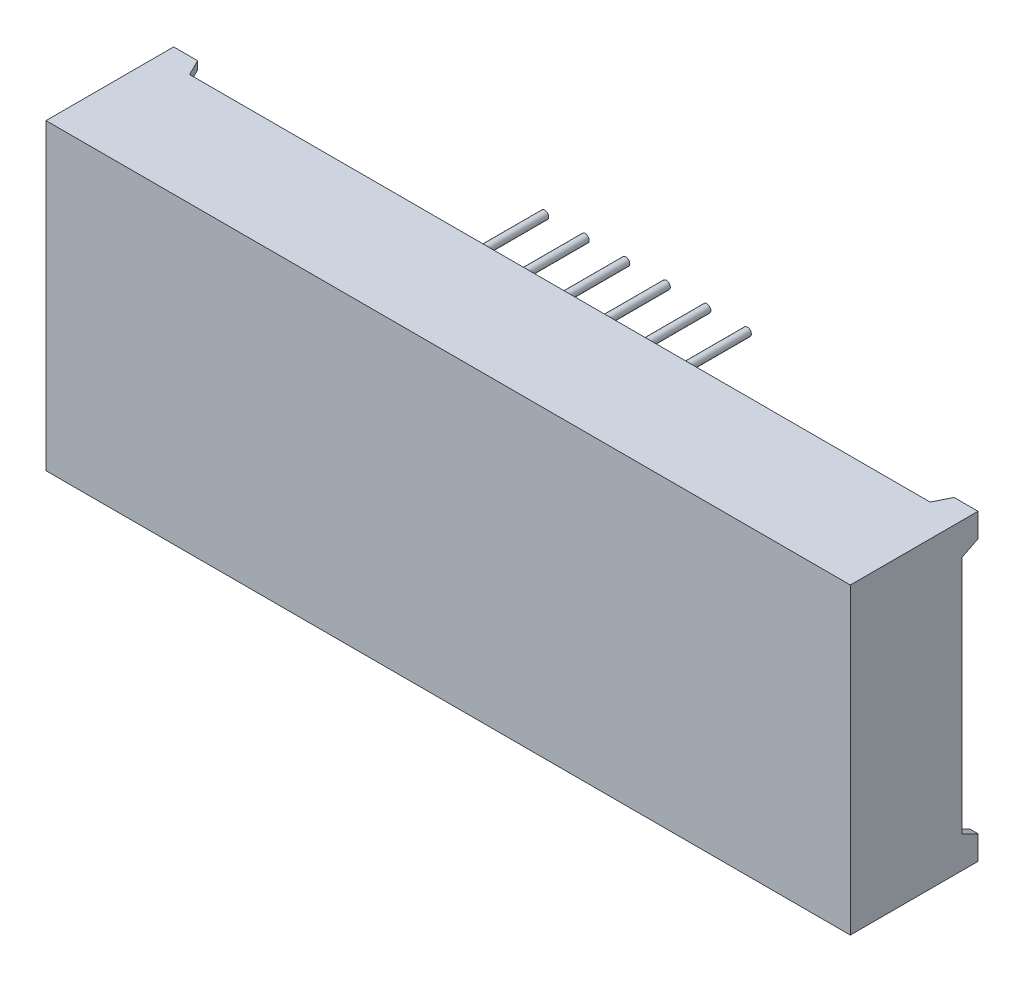
SolidWorks part; units mm, degrees
ref_plane "Front Plane" through (0, 0, 0) normal (0, 0, 1) x (1, 0, 0)
ref_plane "Top Plane" through (0, 0, 0) normal (0, 1, 0) x (1, 0, 0)
ref_plane "Right Plane" through (0, 0, 0) normal (1, 0, 0) x (0, 0, -1)
sketch "Sketch1" plane through (0, 0, 0) normal (0, 1, 0) x (1, 0, 0)
  line L1 (0, 0) -> (50.4, 0)
  line L2 (0, 0) -> (0, 8)
  line L3 (0, 8) -> (50.4, 8)
  line L4 (50.4, 0) -> (50.4, 8)
  dimension "D1" = 8
  dimension "D2" = 50.4
extrude "Boss-Extrude1" add sketch "Sketch1" along normal blind 19
sketch "Sketch2" plane through (0, 0, -8) normal (0, 0, -1) x (-1, 0, 0)
  line L0 (-50.4, 17) -> (-49.9, 17)
  line L1 (-50.4, 19) -> (-50.4, 0) construction
  line L2 (-49.9, 17) -> (-49.9, 18.5)
  line L3 (-49.9, 18.5) -> (-48.4, 18.5)
  line L4 (-48.4, 18.5) -> (-48.4, 19)
  line L5 (-50.4, 19) -> (0, 19) construction
  line L6 (-48.4, 19) -> (-2, 19)
  line L7 (-2, 19) -> (-2, 18.5)
  line L8 (-2, 18.5) -> (-0.5, 18.5)
  line L9 (-0.5, 18.5) -> (-0.5, 17)
  line L10 (-0.5, 17) -> (0, 17)
  line L11 (0, 19) -> (0, 0) construction
  line L12 (0, 17) -> (0, 2)
  line L13 (0, 2) -> (-0.5, 2)
  line L14 (-0.5, 2) -> (-0.5, 0.5)
  line L15 (-0.5, 0.5) -> (-2, 0.5)
  line L16 (-2, 0.5) -> (-2, 0)
  line L17 (-50.4, 0) -> (0, 0) construction
  line L18 (-2, 0) -> (-48.4, 0)
  line L19 (-48.4, 0) -> (-48.4, 0.5)
  line L20 (-48.4, 0.5) -> (-49.9, 0.5)
  line L21 (-49.9, 0.5) -> (-49.9, 2)
  line L22 (-49.9, 2) -> (-50.4, 2)
  line L23 (-50.4, 2) -> (-50.4, 17)
  line L24 (-49.9, 17) -> (-49.9, 2) construction
  line L25 (-48.4, 0.5) -> (-2, 0.5) construction
  line L26 (-0.5, 2) -> (-0.5, 17) construction
  line L27 (-2, 18.5) -> (-48.4, 18.5) construction
  line L28 (-2, 0.5) -> (-2, 18.5) construction
  line L29 (-0.5, 17) -> (-49.9, 17) construction
  line L30 (-48.4, 0.5) -> (-48.4, 18.5) construction
  line L31 (-49.9, 2) -> (-0.5, 2) construction
  dimension "D1" = 0.5
  dimension "D2" = 2
  dimension "D3" = 2
  dimension "D4" = 2
  dimension "D5" = 2
extrude "Cut-Extrude1" cut sketch "Sketch2" against normal blind 1
chamfer "Chamfer1" distance 0.5 distance2 1 8 edges at (50.15, 2, -8) (48.4, 0.25, -8) (2, 0.25, -8) (0.25, 2, -8) (2, 18.75, -8) (0.25, 17, -8) (48.4, 18.75, -8) (50.15, 17, -8) first distance on face at (49.5667, 0.8333, -8) first distance on face at (0.8333, 0.8333, -8) first distance on face at (0.8333, 18.1667, -8) first distance on face at (49.5667, 18.1667, -8)
sketch "Sketch3" plane through (0, 0, -7) normal (0, 0, -1) x (-1, 0, 0)
  line L21 (-49.9, 0.5) -> (-0.5, 0.5)
  line L22 (-49.9, 0.5) -> (-49.9, 18.5)
  line L23 (-49.9, 18.5) -> (-0.5, 18.5)
  line L24 (-0.5, 0.5) -> (-0.5, 18.5)
extrude "Cut-Extrude2" cut sketch "Sketch3" against normal blind 0.1
sketch "Sketch4" plane through (0, 0, -6.9) normal (0, 0, -1) x (-1, 0, 0)
  line L0 (-49.9, 9.5) -> (-0.5, 9.5) construction
  line L1 (-49.9, 2) -> (-49.9, 17) construction
  line L2 (-0.5, 0.5) -> (-0.5, 18.5) construction
  line L3 (-49.9, 17.12) -> (-0.5, 17.12) construction
  line L4 (-49.9, 18.5) -> (-49.9, 0.5) construction
  line L5 (-0.5, 1.88) -> (-49.9, 1.88) construction
  line L6 (-25.2, 1.88) -> (-25.2, 17.12) construction
  line L7 (-26.47, 17.12) -> (-25.2, 15.85) construction
  line L8 (-25.2, 15.85) -> (-23.93, 17.12) construction
  line L9 (-31.55, 17.12) -> (-31.55, 1.88) construction
  line L10 (-29.01, 17.12) -> (-29.01, 1.88) construction
  line L11 (-26.47, 17.12) -> (-26.47, 1.88) construction
  line L12 (-23.93, 17.12) -> (-23.93, 1.88) construction
  line L13 (-21.39, 17.12) -> (-21.39, 1.88) construction
  line L14 (-18.85, 17.12) -> (-18.85, 1.88) construction
  circle A0 centre (-31.55, 17.12) radius 0.25
  circle A1 centre (-29.01, 17.12) radius 0.25
  circle A2 centre (-26.47, 17.12) radius 0.25
  circle A3 centre (-23.93, 17.12) radius 0.25
  circle A4 centre (-21.39, 17.12) radius 0.25
  circle A5 centre (-18.85, 17.12) radius 0.25
  circle A6 centre (-31.55, 1.88) radius 0.25
  circle A7 centre (-29.01, 1.88) radius 0.25
  circle A8 centre (-26.47, 1.88) radius 0.25
  circle A10 centre (-23.93, 1.88) radius 0.25
  circle A11 centre (-21.39, 1.88) radius 0.25
  circle A12 centre (-18.85, 1.88) radius 0.25
  point P30 (-25.2, 9.5)
  dimension "D6" = 0.5
  dimension "D1" = 15.24
  dimension "D2" = 2.54
  dimension "D3" = 2.54
  dimension "D4" = 2.54
  dimension "D5" = 2.54
  dimension "D7" = 2.54
  dimension "D8" = 45
  dimension "D9" = 45
extrude "Boss-Extrude2" add sketch "Sketch4" along normal blind 5.5
sketch "Sketch5" plane through (0, 0, 0) normal (0, 0, 1) x (1, 0, 0)
  line L0 (0, 9.5) -> (50.4, 9.5) construction
  line L1 (0, 19) -> (0, 0) construction
  line L2 (50.4, 19) -> (50.4, 0) construction
  line L3 (49.0088, 15.4806) -> (48.1824, 9.6)
  line L4 (0, 19) -> (50.4, 19) construction
  line L5 (0, 0) -> (50.4, 0) construction
  line L6 (6.15, 19) -> (6.15, 0) construction
  line L7 (18.85, 0) -> (18.85, 19) construction
  line L8 (31.55, 0) -> (31.55, 19) construction
  line L9 (44.25, 0) -> (44.25, 19) construction
  line L10 (25.2, 9.5) -> (25.2, 19) construction
  line L11 (25.2, 14.25) -> (18.85, 14.25) construction
  line L12 (25.2, 14.25) -> (31.55, 14.25) construction
  line L13 (50.4, 16.61) -> (0, 16.61) construction
  line L14 (50.4, 2.39) -> (0, 2.39) construction
  line L15 (49.4, 16.61) -> (49.4, 9.5) construction
  line L16 (49.4, 9.5) -> (49.4, 2.39) construction
  line L17 (48.1824, 9.6) -> (47.6288, 9.6)
  line L18 (47.6288, 9.6) -> (47.2288, 10)
  line L19 (47.2288, 10) -> (48.1577, 16.61)
  line L20 (48.1824, 9.6) -> (48.1543, 9.4) construction
  line L21 (48.1543, 9.4) -> (47.2887, 3.2411)
  line L22 (48.1543, 9.4) -> (47.6288, 9.4)
  line L23 (47.6288, 9.4) -> (47.0652, 8.8365)
  line L24 (47.0652, 8.8365) -> (46.1592, 2.39)
  line L25 (47.4459, 9.5) -> (46.9459, 9)
  line L26 (46.9459, 9) -> (41.5541, 9)
  line L27 (41.5541, 9) -> (41.0541, 9.5)
  line L28 (41.0541, 9.5) -> (41.5541, 10)
  line L29 (41.5541, 10) -> (46.9459, 10)
  line L30 (46.9459, 10) -> (47.4459, 9.5)
  line L31 (44.25, 9) -> (44.25, 10) construction
  line L32 (47.347, 9.1182) -> (47.2056, 9.2597) construction
  line L33 (47.4288, 9.8) -> (47.2873, 9.6586) construction
  line L34 (46.9459, 10) -> (47.2288, 10) construction
  line L35 (45.9573, 2.39) -> (46.0978, 3.39)
  line L36 (46.0978, 3.39) -> (41.0541, 3.39)
  line L37 (41.0541, 3.39) -> (40.9135, 2.39)
  line L38 (40.9135, 2.39) -> (45.9573, 2.39)
  line L39 (42.0752, 3.39) -> (42.0752, 2.39) construction
  line L43 (40.4553, 9.4) -> (39.8834, 3.4816)
  line L44 (40.4553, 9.4) -> (40.4747, 9.6) construction
  line L45 (41.3551, 8.9162) -> (41.4965, 9.0576) construction
  line L46 (40.7826, 2.39) -> (41.4081, 8.8631)
  line L47 (40.4747, 9.6) -> (41.0657, 15.7159)
  line L48 (41.2712, 10) -> (42.2002, 16.61)
  line L49 (41.5541, 10) -> (41.2712, 10) construction
  line L50 (41.2712, 10) -> (40.8712, 9.6)
  line L51 (40.8712, 9.6) -> (40.4747, 9.6)
  line L52 (44.25, 9.5) -> (44.2005, 9.4505) construction
  line L53 (41.0712, 9.8) -> (41.2127, 9.6586) construction
  line L54 (41.4081, 8.8631) -> (40.8712, 9.4)
  line L55 (40.8712, 9.4) -> (40.4553, 9.4)
  arc A0 (48.1577, 16.61) -> (49.0088, 15.4806) centre (48.0186, 15.6197) cw
  arc A1 (46.1592, 2.39) -> (47.2887, 3.2411) centre (46.2984, 3.3803) ccw
  arc A2 (40.7826, 2.39) -> (39.8834, 3.4816) centre (40.8788, 3.3854) cw
  arc A3 (42.2002, 16.61) -> (41.0657, 15.7159) centre (42.061, 15.6197) ccw
  point P36 (48.1683, 9.5)
  point P51 (44.25, 9.5)
  point P60 (47.347, 9.1182)
  point P66 (41.4215, 9.403)
  point P67 (40.465, 9.5)
  point P83 (41.4081, 8.8631)
  point P84 (41.0541, 3.3854)
  dimension "D8" = 1
  dimension "D10" = 1
  dimension "D20" = 1
  dimension "D24" = 0.2
  dimension "D23" = 1
  dimension "D1" = 12.7
  dimension "D2" = 12.7
  dimension "D3" = 12.7
  dimension "D4" = 14.22
  dimension "D5" = 1
  dimension "D6" = 8
  dimension "D7" = 135
  dimension "D9" = 135
  dimension "D11" = 0.1
  dimension "D12" = 1
  dimension "D13" = 0.2
  dimension "D14" = 1
  dimension "D16" = 0.1
  dimension "D17" = 0.2
  dimension "D19" = 0.2
  dimension "D21" = 135
